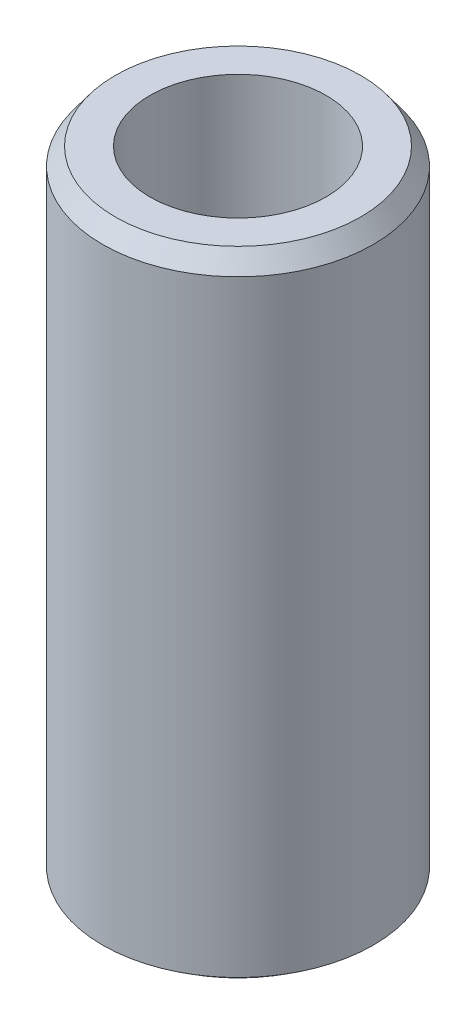
SolidWorks part; units mm, degrees
ref_plane "Front Plane" through (0, 0, 0) normal (0, 0, 1) x (1, 0, 0)
ref_plane "Top Plane" through (0, 0, 0) normal (0, 1, 0) x (1, 0, 0)
ref_plane "Right Plane" through (0, 0, 0) normal (1, 0, 0) x (0, 0, -1)
sketch "Sketch1" plane through (0, 0, 0) normal (0, 1, 0) x (1, 0, 0)
  circle A0 centre (0, 0) radius 17.5
  dimension "SHAFT_OD" = 35
extrude "Boss-Extrude1" add sketch "Sketch1" along normal blind 82.3235
sketch "Sketch2" plane through (0, 0, 0) normal (0, 1, 0) x (1, 0, 0)
  circle A0 centre (0, 0) radius 11.3833
  dimension "BORE_D" = 22.7666
extrude "Cut-Extrude1" cut sketch "Sketch2" along normal through all
chamfer "Chamfer1" distance 2.25 angle 36.134 2 edges at (0, 82.3235, 17.5) (0, 0, 17.5) first distance on face at (0, 82.3235, 17.5) first distance on face at (0, 0, 11.3833)
